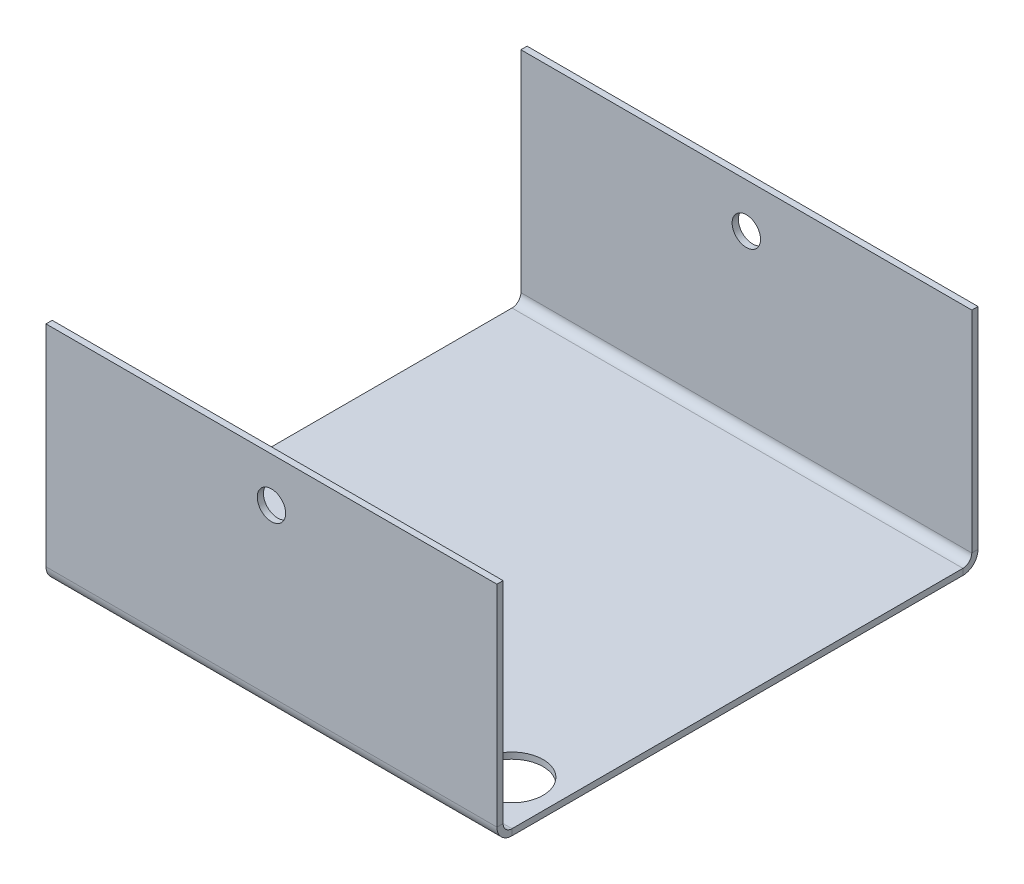
SolidWorks part; units mm, degrees
note: The reader was unsure of these and kept them because the rebuilt part matched: flange length of "Edge-Flange1".
ref_plane "Front Plane" through (0, 0, 0) normal (0, 0, 1) x (1, 0, 0)
ref_plane "Top Plane" through (0, 0, 0) normal (0, 1, 0) x (1, 0, 0)
ref_plane "Right Plane" through (0, 0, 0) normal (1, 0, 0) x (0, 0, -1)
sketch "Sketch1" plane through (0, 0, 0) normal (0, 1, 0) x (1, 0, 0)
  line L1 (-25.4, -25.4) -> (25.4, -25.4)
  line L2 (-25.4, -25.4) -> (-25.4, 25.4)
  line L3 (-25.4, 25.4) -> (25.4, 25.4)
  line L4 (25.4, -25.4) -> (25.4, 25.4)
  line L5 (-25.4, -25.4) -> (25.4, 25.4) construction
  line L6 (-25.4, 25.4) -> (25.4, -25.4) construction
  point P0 (0, 0)
  dimension "D1" = 50.8
  dimension "D2" = 50.8
base flange "Base-Flange1" sketch "Sketch1" thickness 0.7 reverse thickness direction no parameters "D1"=1
edge flange "Edge-Flange1" sketch "Sketch10" flange profiles "Sketch10", "Sketch11" flange angle 90 flange length 25.4 flange position bend outside bend radius 1 thickness 0.7 relief rectangular parameters "D6"=0, "D8"=1
sketch "Sketch10" plane through (0, 0, -25.4) normal (0, 0, -1) x (-1, 0, 0)
  line L2 (-25.4, 0) -> (-25.4, 24.7)
  line L3 (-25.4, 24.7) -> (25.4, 24.7)
  line L4 (25.4, 24.7) -> (25.4, 0)
  line L5 (-25.4, 0) -> (25.4, 0) construction
  line L6 (-25.4, 0) -> (25.4, 0)
sketch "Sketch11" plane through (0, 0, 25.4) normal (0, 0, 1) x (1, 0, 0)
  line L0 (-25.4, 0) -> (25.4, 0) construction
  line L1 (-25.4, 0) -> (25.4, 0)
  line L2 (-25.4, 0) -> (-25.4, 24.7)
  line L3 (-25.4, 24.7) -> (25.4, 24.7)
  line L4 (25.4, 24.7) -> (25.4, 0)
bend "EdgeBend1" bend radius 1 bend angle 90 parameters "D5"=1
bend "EdgeBend2" bend radius 1 bend angle 90 parameters "D5"=2
sketch "Sketch12" plane through (0, 0, 0) normal (0, 1, 0) x (1, 0, 0)
  line L0 (25.4, -25.4) -> (25.4, 25.4) construction
  line L1 (-25.4, -25.4) -> (25.4, -25.4) construction
  circle A0 centre (20.4, -20.4) radius 3.5
  dimension "D1" = 5
  dimension "D3" = 7
  dimension "D2" = 5
extrude "Cut-Extrude1" cut sketch "Sketch12" against normal through all contours A0 normal cut yes
sketch "Sketch13" plane through (0, 0, 0) normal (0, 1, 0) x (1, 0, 0)
  line L0 (25.4, -25.4) -> (25.4, 25.4) construction
  line L1 (-25.4, -25.4) -> (25.4, -25.4) construction
  circle A0 centre (1.4, -20.4) radius 1
  dimension "D1" = 24
  dimension "D2" = 5
extrude "Cut-Extrude2" cut sketch "Sketch13" against normal through all normal cut yes
sketch "Sketch14" plane through (0, 0, 27.1) normal (0, 0, 1) x (1, 0, 0)
  line L0 (25.4, 24.7) -> (-25.4, 24.7) construction
  line L1 (25.4, 1) -> (25.4, 24.7) construction
  circle A0 centre (0, 19.7) radius 1.6
  dimension "D1" = 5
  dimension "D2" = 25.4
extrude "Cut-Extrude3" cut sketch "Sketch14" against normal through all normal cut yes
sketch "Bend-Lines1" [suppressed] plane through (0, 0, 0) normal (0, 1, 0) x (1, 0, 0)
sketch "Bounding-Box1" [suppressed] plane through (0, 0, 0) normal (0, 1, 0) x (1, 0, 0)
sheet metal parameters "Sheet-Metal1" thickness 0.7 parameters "D1"=1
flat pattern "Flat-Pattern1" [suppressed]
sketch "Bend-Lines2" plane through (0, 0, 0) normal (0, 1, 0) x (1, 0, 0)
sketch "Bounding-Box2" [suppressed] plane through (0, 0, 0) normal (0, 1, 0) x (1, 0, 0)
sheet metal parameters "Sheet-Metal2" thickness 0.7 parameters "D1"=1
flat pattern "Flat-Pattern1" [suppressed]
sketch "Bend-Lines2" plane through (0, 0, 0) normal (0, 1, 0) x (1, 0, 0)
sketch "Bounding-Box2" [suppressed] plane through (0, 0, 0) normal (0, 1, 0) x (1, 0, 0)
bend of the flat pattern "Flatten-<EdgeBend1>1"
bend of the flat pattern "Flatten-<EdgeBend2>1"
sheet metal parameters "Sheet-Metal3" thickness 0.7 parameters "D1"=1
flat pattern "Flat-Pattern1" [suppressed]
sketch "Bend-Lines2" plane through (0, 0, 0) normal (0, 1, 0) x (1, 0, 0)
sketch "Bounding-Box2" [suppressed] plane through (0, 0, 0) normal (0, 1, 0) x (1, 0, 0)
bend of the flat pattern "Flatten-<EdgeBend1>1"
bend of the flat pattern "Flatten-<EdgeBend2>1"
sheet metal parameters "Sheet-Metal4" thickness 0.7 parameters "D1"=1
flat pattern "Flat-Pattern1" [suppressed]
sketch "Bend-Lines2" plane through (0, 0, 0) normal (0, 1, 0) x (1, 0, 0)
sketch "Bounding-Box2" [suppressed] plane through (0, 0, 0) normal (0, 1, 0) x (1, 0, 0)
bend of the flat pattern "Flatten-<EdgeBend1>1"
bend of the flat pattern "Flatten-<EdgeBend2>1"
sheet metal parameters "Sheet-Metal5" thickness 0.7 parameters "D1"=1
flat pattern "Flat-Pattern1"
sketch "Bend-Lines2" plane through (0, 0, 0) normal (0, 1, 0) x (1, 0, 0)
  line L0 (-25.4, -26.4603) -> (25.4, -26.4603) construction
  line L1 (25.4, 26.4603) -> (-25.4, 26.4603) construction
  line L2 (-25.4, -26.4603) -> (25.4, -26.4603) construction
  line L3 (25.4, 26.4603) -> (-25.4, 26.4603) construction
sketch3d "Bounding-Box2" [suppressed]
  line L0 (-25.4, -76.6206, 0) -> (-25.4, 76.6206, 0) construction
  line L1 (25.4, -76.6206, 0) -> (25.4, 76.6206, 0) construction
  line L2 (-25.4, -76.6206, 0) -> (25.4, -76.6206, 0) construction
  line L3 (-25.4, 76.6206, 0) -> (25.4, 76.6206, 0) construction
bend of the flat pattern "Flatten-<EdgeBend1>1"
bend of the flat pattern "Flatten-<EdgeBend2>1"
